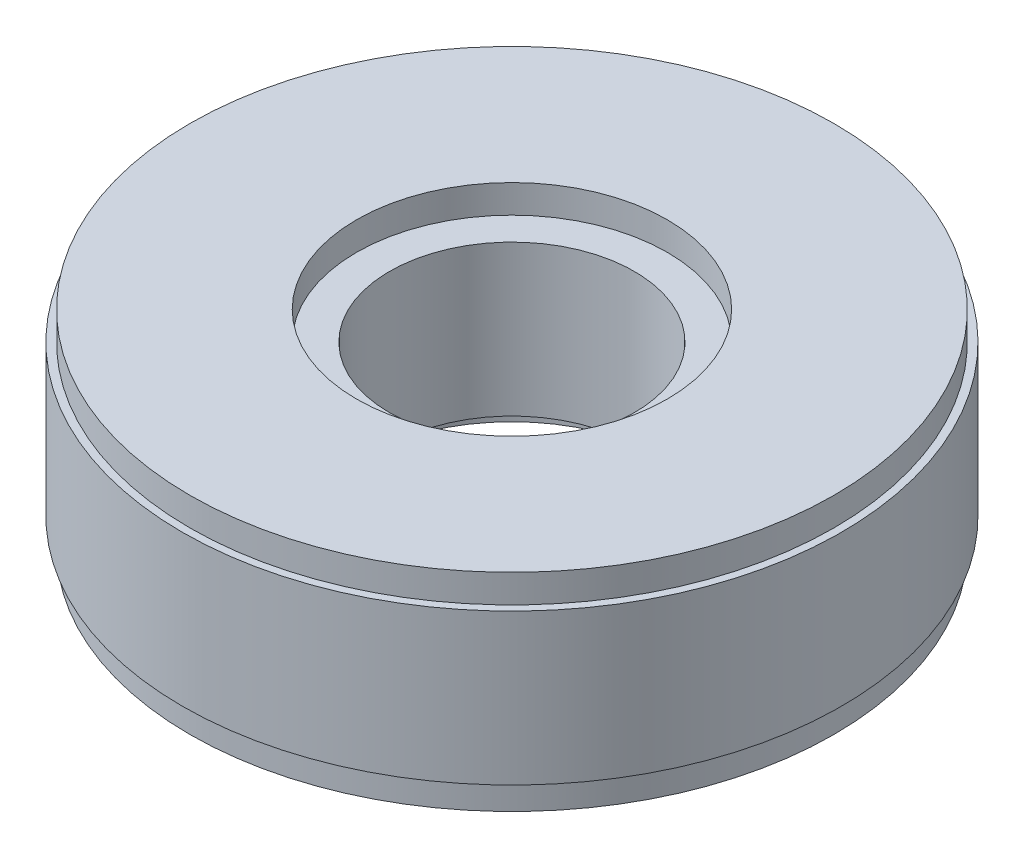
SolidWorks part; units mm, degrees
ref_plane "Front" through (0, 0, 0) normal (0, 0, 1) x (1, 0, 0)
ref_plane "Top" through (0, 0, 0) normal (0, 1, 0) x (1, 0, 0)
ref_plane "Right" through (0, 0, 0) normal (1, 0, 0) x (0, 0, -1)
sketch "Sketch1" plane through (0, 0, 0) normal (0, 1, 0) x (1, 0, 0)
  circle A0 centre (0, 0) radius 6.5
  circle A1 centre (0, 0) radius 17.5
  dimension "D1" = 13
  dimension "D2" = 35
extrude "Boss-Extrude1" add sketch "Sketch1" along normal mid plane 8
sketch "Sketch2" plane through (0, 4, 0) normal (0, 1, 0) x (1, 0, 0)
  circle A0 centre (0, 0) radius 17.1
  circle A1 centre (0, 0) radius 8.25
  dimension "D1" = 34.2
  dimension "D2" = 16.5
extrude "Boss-Extrude2" add sketch "Sketch2" along normal blind 1.5
mirror "Mirror1" about plane through (0, 0, 0) normal (0, 1, 0) of "Boss-Extrude2"
